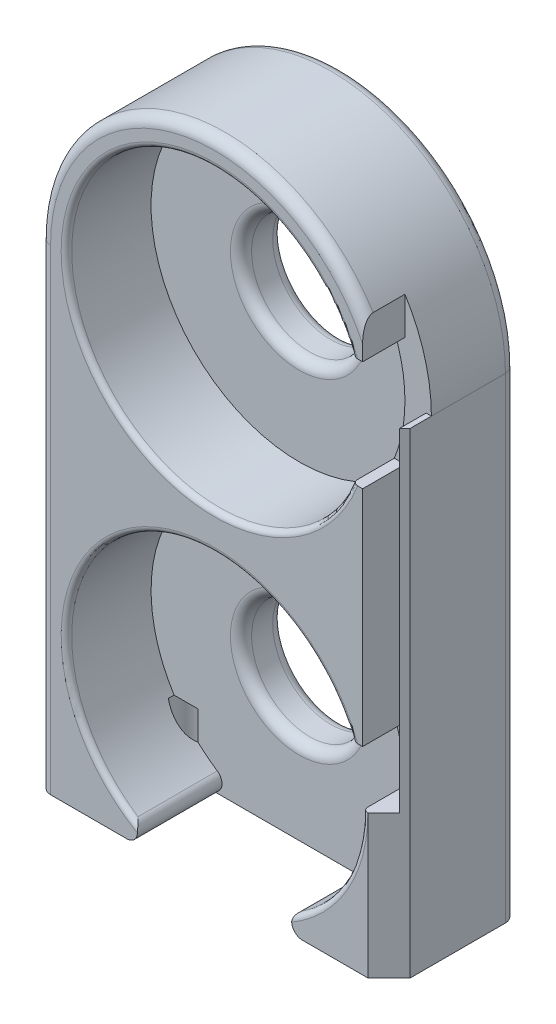
SolidWorks part; units mm, degrees
material "ABS"
ref_plane "Plano frontal" through (0, 0, 0) normal (0, 0, 1) x (1, 0, 0)
ref_plane "Plano superior" through (0, 0, 0) normal (0, 1, 0) x (1, 0, 0)
ref_plane "Plano direito" through (0, 0, 0) normal (1, 0, 0) x (0, 0, -1)
sketch "Esboço1" plane through (0, 0, 0) normal (0, 0, 1) x (1, 0, 0)
  line L2 (-16.5, 0) -> (-16.5, 45)
  line L3 (16.5, 45) -> (16.5, 0)
  line L7 (0, 0) -> (0, 13.5) construction
  line L8 (0, 13.5) -> (0, 45) construction
  line L10 (-16.5, 0) -> (16.5, 0)
  arc A0 (-16.5, 45) -> (16.5, 45) centre (0, 45) cw
  circle A1 centre (0, 13.5) radius 9 construction
  circle A2 centre (0, 45) radius 9 construction
  circle A3 centre (0, 45) radius 5.5
  circle A4 centre (0, 13.5) radius 5.5
  dimension "D5" = 18
  dimension "D7" = 18
  dimension "D8" = 11
  dimension "D9" = 11
  dimension "D1" = 33
  dimension "D4" = 13.5
  dimension "D6" = 31.5
extrude "Ressalto-extrusão1" add sketch "Esboço1" along normal blind 12
sketch "Esboço2" plane through (0, 0, 12) normal (0, 0, 1) x (1, 0, 0)
  line L0 (0, 45) -> (0, 59) construction
  circle A0 centre (0, 45) radius 14
  circle A1 centre (0, 13.5) radius 14
  dimension "D1" = 28
  dimension "D2" = 28
extrude "Corte-extrusão1" cut sketch "Esboço2" against normal blind 8
sketch "Esboço4" plane through (0, 0, 0) normal (0, 0, -1) x (-1, 0, 0)
  line L0 (0, 45) -> (0, 54) construction
  line L1 (0, 13.5) -> (0, 22.5) construction
  line L2 (0, 45) -> (7.7942, 40.5) construction
  line L3 (0, 45) -> (-7.7942, 40.5) construction
  line L4 (0, 13.5) -> (7.7942, 9) construction
  line L5 (0, 13.5) -> (-7.7942, 9) construction
  dimension "D1" = 9
  dimension "D2" = 9
  dimension "D3" = 3
  dimension "D4" = 3
sketch "Esboço5" plane through (0, 0, 12) normal (0, 0, 1) x (1, 0, 0)
  line L4 (16, 13.5) -> (16, 45)
  line L5 (16, 53.7321) -> (14, 53.7321)
  line L6 (14, 53.7321) -> (14, 50.1962)
  line L7 (13, 50.1962) -> (14, 50.1962)
  line L8 (13, 50.1962) -> (13, 39.8038)
  line L9 (13, 39.8038) -> (14, 39.8038)
  line L10 (14, 39.8038) -> (14, 18.6962)
  line L11 (14, 18.6962) -> (13, 18.6962)
  line L12 (13, 18.6962) -> (13, 13.5)
  line L14 (13, 13.5) -> (14, 13.5)
  line L15 (14, 13.5) -> (16, 13.5)
  line L16 (0, 13.5) -> (14, 13.5) construction
  line L17 (16, 49.0311) -> (18, 49.0311)
  line L18 (18, 49.0311) -> (18, 45)
  line L19 (18, 45) -> (16.5, 45)
  line L20 (16.5, 45) -> (16, 45)
  line L21 (16, 49.0311) -> (16, 53.7321)
  circle A1 centre (0, 45) radius 14 construction
  circle A3 centre (0, 13.5) radius 14 construction
  arc A4 (16.5, 45) -> (-16.5, 45) centre (0, 45) ccw construction
  circle A5 centre (0, 45) radius 14 construction
  circle A6 centre (0, 13.5) radius 14 construction
  dimension "D1" = 2
  dimension "D2" = 1
  dimension "D3" = 1
  dimension "D4" = 2
  dimension "D5" = 1
  dimension "D6" = 1
  dimension "D7" = 2
extrude "Corte-extrusão2" cut sketch "Esboço5" against normal offset from surface (4 mm away) 4 up to face at (5.5, 45, 4)
fillet "Filete7" radius 1 9 edges at (-16.5, 22.5, 12) (16.5, 22.5, 0) (0, 61.5, 0) (5.5, 45, 4) (5.5, 45, 0) (5.5, 13.5, 4) (5.5, 13.5, 0) (-4.5415, 60.8627, 12) (-16.5, 22.5, 0)
fillet "Filete9" radius 0.5 3 edges at (-14, 45, 12) (11.1336, 5.0122, 12) (-10.4389, 22.8289, 12)
sketch "Esboço6" plane through (0, 0, 0) normal (0, -1, 0) x (1, 0, 0)
  line L0 (-15.5, 0) -> (15.5, 0) construction
  line L1 (-11, 3) -> (11, 3) construction
  line L2 (-14, 9) -> (14, 9) construction
  line L5 (-15.5, 12) -> (-5.2915, 12) construction
  circle A0 centre (-14, 9) radius 1.75
  circle A1 centre (14, 9) radius 1.75
  circle A2 centre (11, 3) radius 1.75
  circle A3 centre (-11, 3) radius 1.75
  point P0 (-11, 3)
  point P1 (11, 3)
  point P2 (14, 9)
  point P3 (-14, 9)
  point P4 (0, 3)
  point P13 (0, 9)
  dimension "D6" = 3.5
  dimension "D1" = 3
  dimension "D2" = 22
  dimension "D3" = 28
  dimension "D4" = 3
extrude "Corte-extrusão3" cut sketch "Esboço6" against normal blind 6
chamfer "Chanfro1" distance 2 angle 45 1 edges at (16.5, 22.5, 12)
fillet "Filete10" radius 1 2 edges at (3.7081, 0, 7.75) (-3.7081, 0, 7.75)
